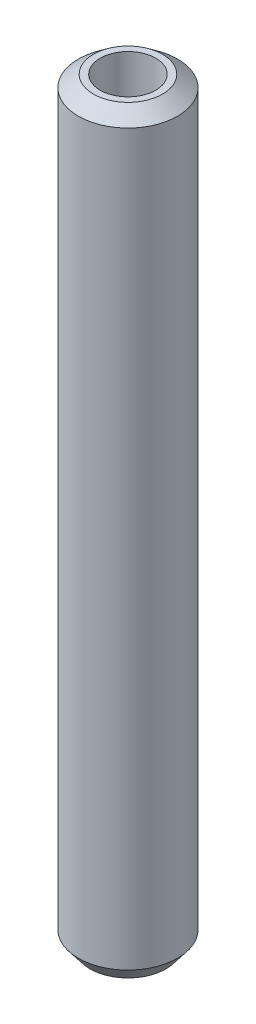
SolidWorks part; units mm, degrees
ref_plane "Front Plane" through (0, 0, 0) normal (0, 0, 1) x (1, 0, 0)
ref_plane "Top Plane" through (0, 0, 0) normal (0, 1, 0) x (1, 0, 0)
ref_plane "Right Plane" through (0, 0, 0) normal (1, 0, 0) x (0, 0, -1)
sketch "Sketch1" plane through (0, 0, 0) normal (0, 1, 0) x (1, 0, 0)
  circle A0 centre (0, 0) radius 20
  dimension "SHAFT_OD" = 40
extrude "Boss-Extrude1" add sketch "Sketch1" along normal blind 304.8777
sketch "Sketch2" plane through (0, 0, 0) normal (0, 1, 0) x (1, 0, 0)
  circle A0 centre (0, 0) radius 11.2077
  dimension "BORE_D" = 22.4155
extrude "Cut-Extrude1" cut sketch "Sketch2" along normal through all
chamfer "Chamfer1" distance 4.6906 angle 52.328 2 edges at (0, 304.8777, 20) (0, 0, 20) first distance on face at (0, 304.8777, 20) first distance on face at (0, 0, 11.2077)
